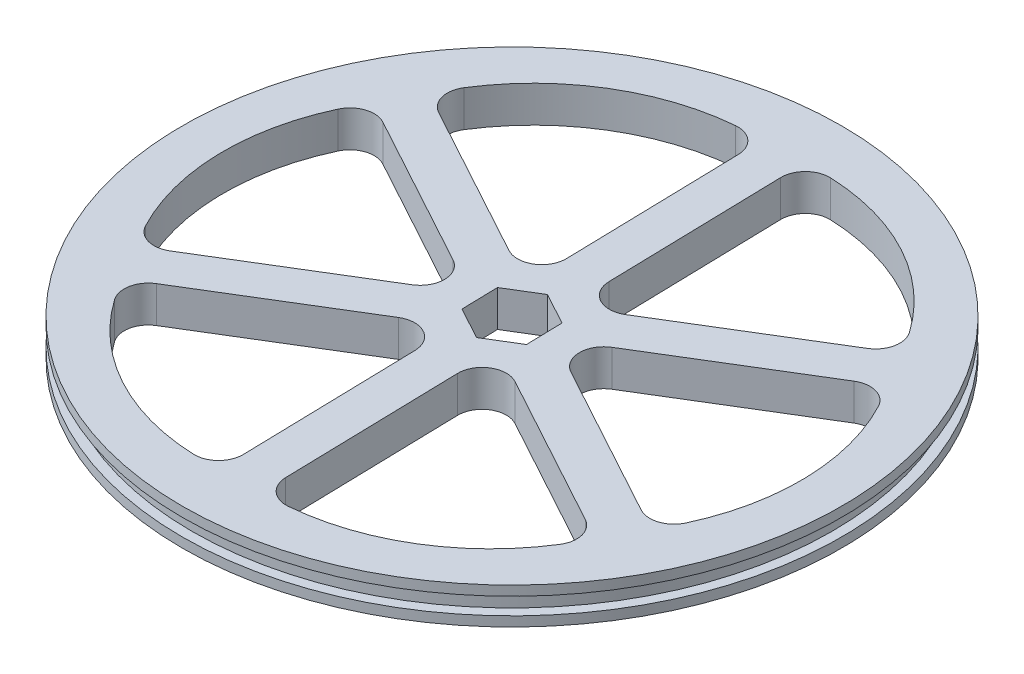
SolidWorks part; units mm, degrees
ref_plane "Front Plane" through (0, 0, 0) normal (0, 0, 1) x (1, 0, 0)
ref_plane "Top Plane" through (0, 0, 0) normal (0, 1, 0) x (1, 0, 0)
ref_plane "Right Plane" through (0, 0, 0) normal (1, 0, 0) x (0, 0, -1)
sketch "Sketch1" plane through (0, 0, 0) normal (0, 1, 0) x (1, 0, 0)
  circle A0 centre (0, 0) radius 68
  circle A1 centre (0, 0) radius 66
extrude "Boss-Extrude1" add sketch "Sketch1" along normal blind 7.5 contours A1
extrude "Boss-Extrude3" add sketch "Sketch1<4>" along normal blind 2
sketch "Sketch1<4>" plane through (0, 0, 0) normal (0, 1, 0) x (1, 0, 0) same geometry as "Sketch1"
sketch "Sketch4" plane through (0, 7.5, 0) normal (0, 1, 0) x (1, 0, 0)
  circle A0 centre (0, 0) radius 68
extrude "Boss-Extrude4" add sketch "Sketch4" against normal blind 2
sketch "Sketch6" plane through (0, 7.5, 0) normal (0, 1, 0) x (1, 0, 0)
  line L1 (-6.5891, 3.5941) -> (-6.4071, -3.9093)
  line L2 (-6.4071, -3.9093) -> (0.182, -7.5033)
  line L3 (0.182, -7.5033) -> (6.5891, -3.5941)
  line L4 (6.5891, -3.5941) -> (6.4071, 3.9093)
  line L5 (6.4071, 3.9093) -> (-0.182, 7.5033)
  line L6 (-0.182, 7.5033) -> (-6.5891, 3.5941)
  circle A0 centre (0, 0) radius 6.5 construction
extrude "Cut-Extrude1" cut sketch "Sketch6" against normal through all
sketch "Sketch7" plane through (0, 7.5, 0) normal (0, 1, 0) x (1, 0, 0)
  line L2 (-4.4273, 7.256) -> (-48.322, 31.1986)
  line L3 (-4.4273, 7.256) -> (-5.6397, 57.2413)
  arc A0 (-48.322, 31.1986) -> (-5.6397, 57.2413) centre (-6.9599, 11.4068) cw
  dimension "D1" = 60
extrude "Cut-Extrude2" cut sketch "Sketch7" against normal through all contours L3 A0 L2
fillet "Fillet1" radius 5 3 edges at (-4.4273, 3.75, -7.256) (-5.6397, 3.75, -57.2413) (-48.322, 3.75, -31.1986)
sketch "Sketch8" plane through (0, 0, 0) normal (1, 0, 0) x (0, 0, -1)
  line L0 (0, 0) -> (0, 25)
pattern_circular "CirPattern1" count 6 every 60 about axis through (0, 0, 0) along (0, 1, 0) of "Cut-Extrude2", "Fillet1"
